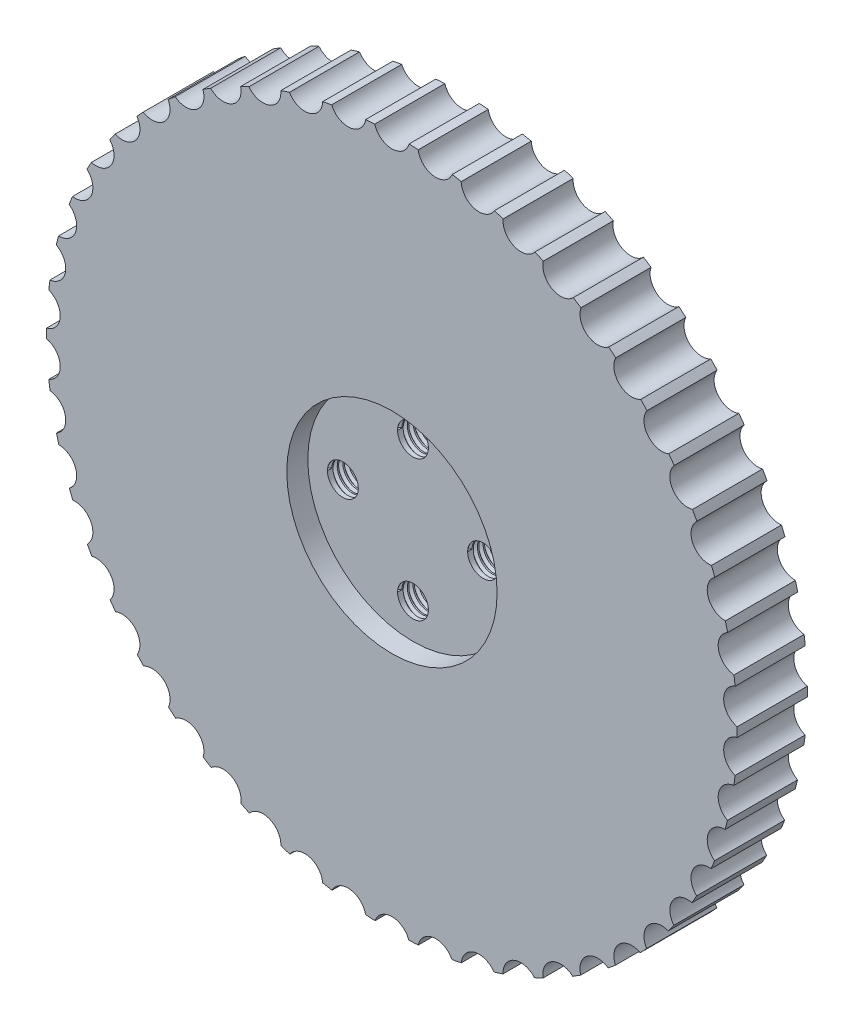
SolidWorks part; units mm, degrees
ref_plane "Ebene vorne" through (0, 0, 0) normal (0, 0, 1) x (1, 0, 0)
ref_plane "Ebene oben" through (0, 0, 0) normal (0, 1, 0) x (1, 0, 0)
ref_plane "Ebene rechts" through (0, 0, 0) normal (1, 0, 0) x (0, 0, -1)
sketch "Skizze1" plane through (0, 0, 0) normal (0, 0, 1) x (1, 0, 0)
  circle A0 centre (0, 0) radius 100
extrude "Aufsatz-Linear austragen1" add sketch "Skizze1" along normal blind 10
sketch "Skizze3" plane through (0, 0, 10) normal (0, 0, 1) x (1, 0, 0)
  circle A0 centre (0, 0) radius 49.9
  dimension "D1" = 99.8
extrude "Schnitt-Linear austragen2" cut sketch "Skizze3" against normal blind 20 flip side to cut
sketch "Skizze6" plane through (0, 0, 10) normal (0, 0, 1) x (1, 0, 0)
  circle A0 centre (0, 49.9) radius 2.55
  circle A1 centre (0, 0) radius 49.9 construction
  dimension "D1" = 5.1
extrude "Schnitt-Linear austragen3" cut sketch "Skizze6" against normal blind 20
pattern_circular "Kreismuster3" count 50 over 360 about axis through (0, -0.0631, 0) along (0, 0, 1) of "Schnitt-Linear austragen3"
sketch "Skizze7" plane through (0, 0, 10) normal (0, 0, 1) x (1, 0, 0)
  circle A0 centre (0, 0) radius 49.25
  dimension "D1" = 98.5
extrude "Schnitt-Linear austragen4" cut sketch "Skizze7" against normal blind 20 flip side to cut
sketch "Skizze8" plane through (0, 0, 10) normal (0, 0, 1) x (1, 0, 0)
  circle A0 centre (0, 0) radius 15
  dimension "D1" = 30
extrude "Schnitt-Linear austragen5" cut sketch "Skizze8" against normal blind 3
sketch "Skizze9" plane through (0, 0, 0) normal (0, 0, -1) x (-1, 0, 0)
  circle A0 centre (0, 0) radius 15
  dimension "D1" = 30
extrude "Schnitt-Linear austragen6" cut sketch "Skizze9" against normal blind 3
sketch "Skizze10" plane through (0, 0, 7) normal (0, 0, 1) x (1, 0, 0)
  circle A0 centre (10, 0) radius 2.2
  circle A1 centre (-10, 0) radius 2.2
  circle A2 centre (0, -10) radius 2.2
  circle A3 centre (0, 10) radius 2.2
  dimension "D3" = 4.4
  dimension "D4" = 4.4
  dimension "D7" = 4.4
  dimension "D8" = 4.4
  dimension "D1" = 10
  dimension "D2" = 10
  dimension "D5" = 10
  dimension "D6" = 10
extrude "Schnitt-Linear austragen7" cut sketch "Skizze10" against normal blind 5
thread "Gewinde1" pitch 0.8 start angle 0, offset 0, length 20, pitch 0.8, diameter 4.4
ref_plane "Ebene1" through (-2.2, 10, 7) normal (0, -1, 0) x (-1, 0, 0)
sketch "Gewindeprofil1" plane through (-2.2, 10, 7) normal (0, -1, 0) x (-1, 0, 0)
  line L0 (0, 0) -> (0, 0.8) construction
  line L1 (0, 0) -> (0.433, 0.25)
  line L2 (0.433, 0.25) -> (0.433, 0.35)
  line L3 (0.433, 0.35) -> (0, 0.6)
  line L4 (0.433, 0.3) -> (0, 0.3) construction
  line L11 (0, 0) -> (0, 0.6)
  point P2 (0, 0)
  dimension "Pitch" = 0.8
  dimension "Profile_Angle" = 60
  dimension "Profile_Land" = 0.1
  dimension "Profile_Height" = 0.433
thread "Gewinde2" pitch 0.8 profile "Gewindeprofil2" start angle 0, offset 0, length 20, pitch 0.8, diameter 4.4
ref_plane "Ebene2" through (-12.2, 0, 7) normal (0, -1, 0) x (-1, 0, 0)
sketch "Gewindeprofil2" plane through (-12.2, 0, 7) normal (0, -1, 0) x (-1, 0, 0)
  line L0 (0, 0) -> (0, 0.8) construction
  line L1 (0, 0) -> (0.433, 0.25)
  line L2 (0.433, 0.25) -> (0.433, 0.35)
  line L3 (0.433, 0.35) -> (0, 0.6)
  line L4 (0.433, 0.3) -> (0, 0.3) construction
  line L11 (0, 0) -> (0, 0.6)
  point P2 (0, 0)
  dimension "Pitch" = 0.8
  dimension "Profile_Angle" = 60
  dimension "Profile_Land" = 0.1
  dimension "Profile_Height" = 0.433
thread "Gewinde3" pitch 0.8 profile "Gewindeprofil3" start angle 0, offset 0, length 20, pitch 0.8, diameter 4.4
ref_plane "Ebene3" through (-2.2, -10, 7) normal (0, -1, 0) x (-1, 0, 0)
sketch "Gewindeprofil3" plane through (-2.2, -10, 7) normal (0, -1, 0) x (-1, 0, 0)
  line L0 (0, 0) -> (0, 0.8) construction
  line L1 (0, 0) -> (0.433, 0.25)
  line L2 (0.433, 0.25) -> (0.433, 0.35)
  line L3 (0.433, 0.35) -> (0, 0.6)
  line L4 (0.433, 0.3) -> (0, 0.3) construction
  line L11 (0, 0) -> (0, 0.6)
  point P2 (0, 0)
  dimension "Pitch" = 0.8
  dimension "Profile_Angle" = 60
  dimension "Profile_Land" = 0.1
  dimension "Profile_Height" = 0.433
thread "Gewinde4" pitch 0.8 profile "Gewindeprofil4" start angle 0, offset 0, length 20, pitch 0.8, diameter 4.4
ref_plane "Ebene4" through (7.8, 0, 7) normal (0, -1, 0) x (-1, 0, 0)
sketch "Gewindeprofil4" plane through (7.8, 0, 7) normal (0, -1, 0) x (-1, 0, 0)
  line L0 (0, 0) -> (0, 0.8) construction
  line L1 (0, 0) -> (0.433, 0.25)
  line L2 (0.433, 0.25) -> (0.433, 0.35)
  line L3 (0.433, 0.35) -> (0, 0.6)
  line L4 (0.433, 0.3) -> (0, 0.3) construction
  line L11 (0, 0) -> (0, 0.6)
  point P2 (0, 0)
  dimension "Pitch" = 0.8
  dimension "Profile_Angle" = 60
  dimension "Profile_Land" = 0.1
  dimension "Profile_Height" = 0.433
